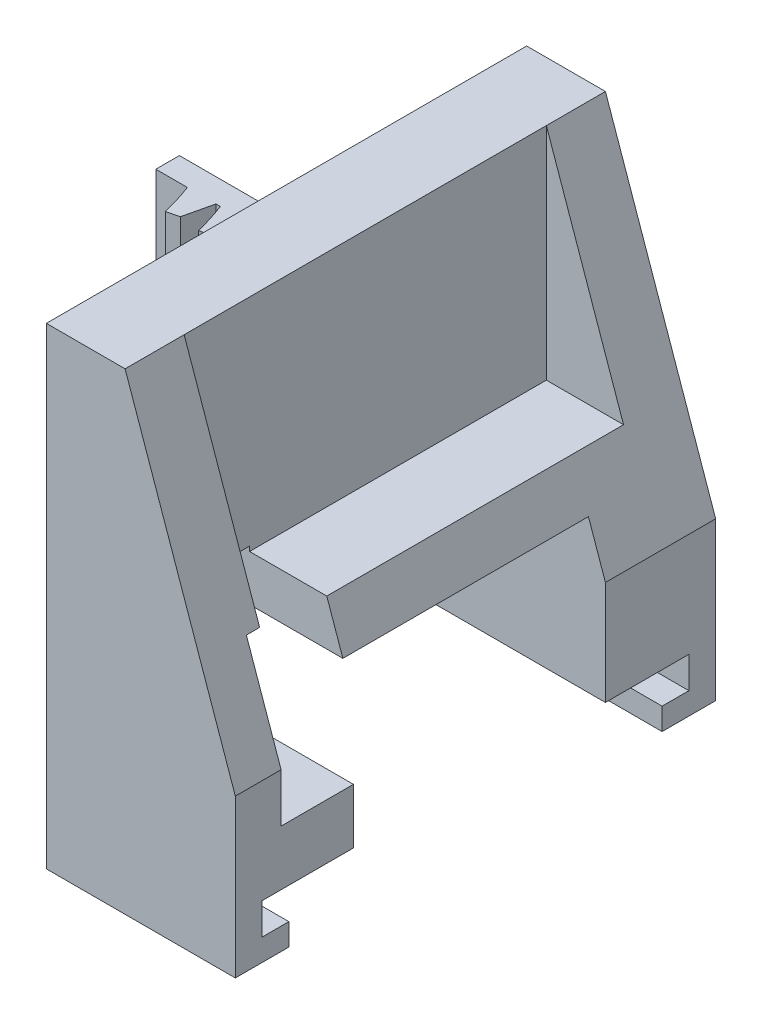
SolidWorks part; units mm, degrees
ref_plane "Front Plane" through (0, 0, 0) normal (0, 0, 1) x (1, 0, 0)
ref_plane "Top Plane" through (0, 0, 0) normal (0, 1, 0) x (1, 0, 0)
ref_plane "Right Plane" through (0, 0, 0) normal (1, 0, 0) x (0, 0, -1)
sketch "Sketch1" plane through (0, 0, 0) normal (0, 0, 1) x (1, 0, 0)
  line L0 (0, 0) -> (0, -30)
  line L1 (0, -30) -> (12, -30)
  line L2 (12, -30) -> (12, -20)
  line L3 (12, -20) -> (5, 0)
  line L4 (5, 0) -> (0, 0)
  dimension "D1" = 30
  dimension "D2" = 12
  dimension "D3" = 10
  dimension "D4" = 5
extrude "Boss-Extrude1" add sketch "Sketch1" against normal blind 30.5
sketch "Sketch4" plane through (0, 0, 0) normal (-1, 0, 0) x (0, 0, 1)
  line L0 (-30.5, 0) -> (-30.5, -30) construction
  line L1 (-23.5, -16.9179) -> (-7.5, -16.9179)
  line L2 (-23.5, -16.9179) -> (-23.5, -30.9179)
  line L3 (-23.5, -30.9179) -> (-7.5, -30.9179)
  line L4 (-7.5, -16.9179) -> (-7.5, -30.9179)
  point P4 (-23.5, -23.9179)
  dimension "D1" = 16
  dimension "D2" = 14
  dimension "D3" = 7
extrude "Cut-Extrude2" cut sketch "Sketch4" against normal blind 25 contours L2 L1 L4 L3
ref_plane "Plane1" through (0, 0, -15.25) normal (0, 0, 1) x (1, 0, 0)
sketch "Sketch6" plane through (0, 0, -15.25) normal (0, 0, 1) x (1, 0, 0)
  line L0 (5, 0) -> (5, -14)
  line L1 (5, -14) -> (9.9, -14)
  line L2 (12, -20) -> (5, 0) construction
  line L3 (9.9, -14) -> (5, 0)
  dimension "D1" = 14
extrude "Cut-Extrude4" cut sketch "Sketch6" against normal mid plane 23
ref_plane "Plane2" through (0, -22, 0) normal (0, 1, 0) x (1, 0, 0)
sketch "Sketch7" plane through (0, -22, 0) normal (0, 1, 0) x (1, 0, 0)
  line L0 (0, 27.45) -> (-19, 27.45)
  line L1 (0, 30.5) -> (0, 0) construction
  line L3 (0, 27.45) -> (0, 25.95)
  line L4 (0, 25.95) -> (-0.5, 25.95)
  line L47 (-0.5, 25.95) -> (-0.9304, 24.1151)
  line L62 (-16.5, 15.25) -> (16.5, 15.25) construction
  line L108 (-19, 25.95) -> (-19, 27.45)
  line L112 (-0.9304, 24.1151) -> (-1.6865, 23.9276)
  line L113 (-2.3144, 25.95) -> (-2.597, 25.95)
  line L114 (-3.0274, 24.1151) -> (-3.7835, 23.9276)
  line L115 (-2.597, 25.95) -> (-3.0274, 24.1151)
  line L116 (-5.1244, 24.1151) -> (-5.8805, 23.9276)
  line L117 (-4.694, 25.95) -> (-5.1244, 24.1151)
  line L118 (-7.2214, 24.1151) -> (-7.9775, 23.9276)
  line L119 (-6.791, 25.95) -> (-7.2214, 24.1151)
  line L120 (-9.3184, 24.1151) -> (-10.0745, 23.9276)
  line L121 (-8.888, 25.95) -> (-9.3184, 24.1151)
  line L122 (-11.4154, 24.1151) -> (-12.1715, 23.9276)
  line L123 (-10.985, 25.95) -> (-11.4154, 24.1151)
  line L124 (-13.5124, 24.1151) -> (-14.2685, 23.9276)
  line L125 (-13.082, 25.95) -> (-13.5124, 24.1151)
  line L126 (-4.4114, 25.95) -> (-4.694, 25.95)
  line L127 (-6.5085, 25.95) -> (-6.791, 25.95)
  line L128 (-8.6055, 25.95) -> (-8.888, 25.95)
  line L129 (-10.7025, 25.95) -> (-10.985, 25.95)
  line L130 (-12.7995, 25.95) -> (-13.082, 25.95)
  line L132 (-15.6094, 24.1151) -> (-16.3655, 23.9276)
  line L133 (-15.179, 25.95) -> (-15.6094, 24.1151)
  line L134 (-14.8965, 25.95) -> (-15.179, 25.95)
  line L135 (-16.9935, 25.95) -> (-19, 25.95)
  arc A0 (-1.6865, 23.9276) -> (-2.3144, 25.95) centre (-19.4305, 19.5266) ccw
  arc A1 (-3.7835, 23.9276) -> (-4.4114, 25.95) centre (-21.5275, 19.5266) ccw
  arc A2 (-5.8805, 23.9276) -> (-6.5085, 25.95) centre (-23.6245, 19.5266) ccw
  arc A3 (-7.9775, 23.9276) -> (-8.6055, 25.95) centre (-25.7215, 19.5266) ccw
  arc A4 (-10.0745, 23.9276) -> (-10.7025, 25.95) centre (-27.8185, 19.5266) ccw
  arc A5 (-12.1715, 23.9276) -> (-12.7995, 25.95) centre (-29.9155, 19.5266) ccw
  arc A6 (-14.2685, 23.9276) -> (-14.8965, 25.95) centre (-32.0125, 19.5266) ccw
  arc A7 (-16.3655, 23.9276) -> (-16.9935, 25.95) centre (-34.1095, 19.5266) ccw
  dimension "D1" = 7
  dimension "D4" = 8
  dimension "D2" = 19
  dimension "D3" = 1.5
  dimension "D6" = 0.5
  dimension "D7" = 12.2
extrude "Boss-Extrude2" add sketch "Sketch7" along normal blind 8
sketch "Sketch8" plane through (0, 0, 0) normal (-1, 0, 0) x (0, 0, 1)
  line L0 (-7.9068, -13.7) -> (-2.9068, -13.7)
  line L2 (-7.5, -30) -> (0, -30) construction
  line L6 (-2.9068, -13.7) -> (-2.9068, -23.1)
  line L7 (-2.9068, -23.1) -> (-7.9068, -23.1)
  line L9 (-7.9068, -23.1) -> (-7.9068, -13.7)
  dimension "D1" = 5
  dimension "D2" = 9.4
  dimension "D3" = 6.9
extrude "Cut-Extrude5" cut sketch "Sketch8" against normal through all
sketch "Sketch9" plane through (0, 0, 0) normal (-1, 0, 0) x (0, 0, 1)
  line L0 (-7.5, -26.6) -> (-1.7, -26.6)
  line L1 (-7.5, -23.1) -> (-7.5, -30) construction
  line L2 (-1.7, -26.6) -> (-1.7, -28.6)
  line L3 (-1.7, -28.6) -> (-3.4, -28.6)
  line L4 (-3.4, -28.6) -> (-3.4, -30.2967)
  line L5 (-3.4, -30.2967) -> (-7.5, -30.2967)
  line L6 (-7.5, -30.2967) -> (-7.5, -26.6)
  line L7 (-7.5, -30) -> (0, -30) construction
  line L8 (-15.25, -16.5) -> (-15.25, 16.5) construction
  line L9 (-23, -30.2967) -> (-23, -26.6)
  line L10 (-27.1, -30.2967) -> (-23, -30.2967)
  line L11 (-27.1, -28.6) -> (-27.1, -30.2967)
  line L12 (-28.8, -28.6) -> (-27.1, -28.6)
  line L13 (-28.8, -26.6) -> (-28.8, -28.6)
  line L14 (-23, -26.6) -> (-28.8, -26.6)
  dimension "D1" = 5.8
  dimension "D2" = 2
  dimension "D3" = 1.4
  dimension "D4" = 1.7
extrude "Cut-Extrude6" cut sketch "Sketch9" against normal through all
